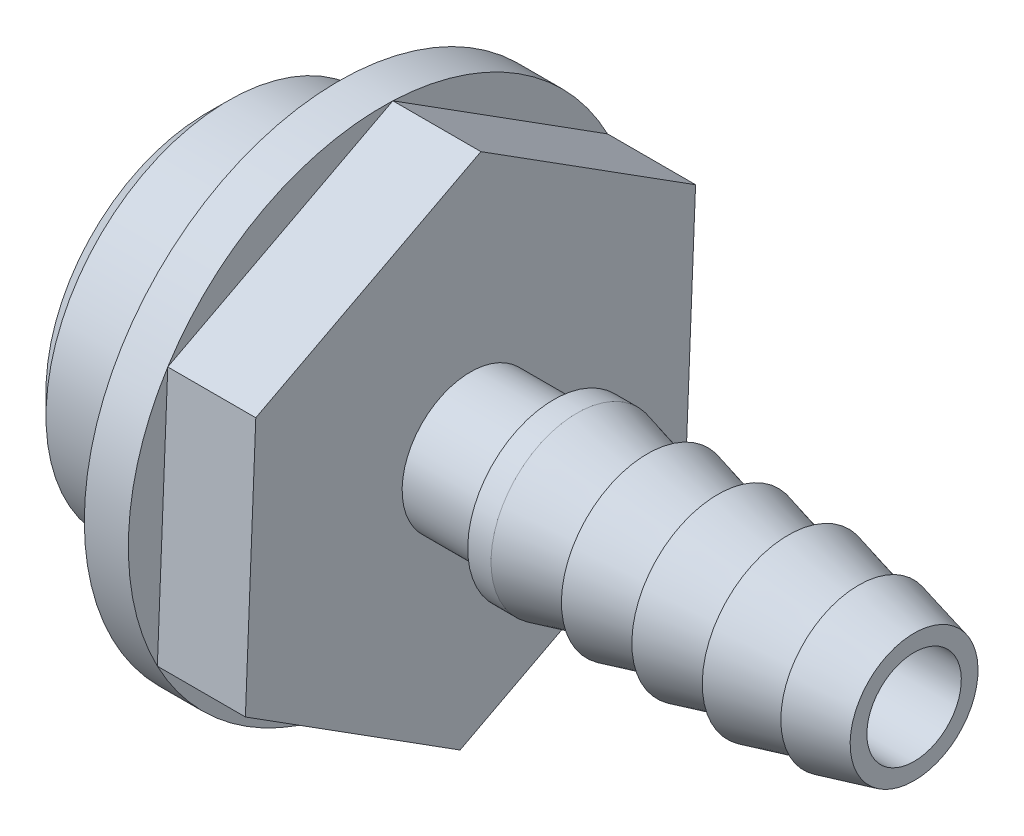
SolidWorks part; units mm, degrees
ref_plane "Plan de face" through (0, 0, 0) normal (0, 0, 1) x (1, 0, 0)
ref_plane "Plan de dessus" through (0, 0, 0) normal (0, 1, 0) x (1, 0, 0)
ref_plane "Plan de droite" through (0, 0, 0) normal (1, 0, 0) x (0, 0, -1)
ref_plane "Plan1"
sketch "Esquisse1" plane through (0, 0, 0) normal (0, 0, 1) x (1, 0, 0)
  line L0 (0, 1.703) -> (16, 1.703)
  line L1 (16, 1.703) -> (16, 3.1)
  line L2 (16, 3.1) -> (14, 3.1)
  line L3 (14, 3.1) -> (14, 2.465)
  line L4 (14, 2.465) -> (11.46, 3.1)
  line L5 (11.46, 3.1) -> (11.46, 2.465)
  line L6 (11.46, 2.465) -> (8.92, 3.1)
  line L7 (8.92, 3.1) -> (8.92, 2.465)
  line L8 (8.92, 2.465) -> (6.38, 3.1)
  line L9 (6.38, 3.1) -> (6.38, 2.465)
  line L10 (6.38, 2.465) -> (3.84, 3.1)
  line L11 (3.84, 3.1) -> (3, 3.1)
  line L12 (3, 3.1) -> (3, 2.465)
  line L13 (3, 2.465) -> (0, 2.465)
  line L14 (0, 2.465) -> (0, 1.703)
  line L15 (0, 0) -> (142.9139, 0) construction
  dimension "D2" = 16
  dimension "D3" = 2
  dimension "D4" = 2.54
  dimension "D5" = 2.54
  dimension "D6" = 2.54
  dimension "D7" = 2.54
  dimension "D8" = 165.964
  dimension "D9" = 16
  dimension "D10" = 16
  dimension "D11" = 3
  dimension "D12" = 0.762
  dimension "D13" = 0.635
  dimension "D14" = 1.397
  dimension "D15" = 3.1
revolve "Revolution1" add sketch "Esquisse1" angle 360 about L15
chamfer "Chamfer1" distance 0.7938 distance2 3.175 1 edges at (16, -3.1, 0) first distance on face at (16, -3.1, 0)
ref_plane "Plan2"
sketch "Esquisse2" plane through (0, 0, 0) normal (-1, 0, 0) x (0, 0, 1)
  line L0 (0.3759, -9.1577) -> (-7.7429, -4.9044)
  line L1 (-7.7429, -4.9044) -> (-8.1188, 4.2533)
  line L2 (-8.1188, 4.2533) -> (-0.3759, 9.1577)
  line L3 (-0.3759, 9.1577) -> (7.7429, 4.9044)
  line L4 (7.7429, 4.9044) -> (8.1188, -4.2533)
  line L5 (8.1188, -4.2533) -> (0.3759, -9.1577)
  dimension "D1" = 15.875
extrude "Extrusion1" add sketch "Esquisse2" along normal blind 3.175
sketch "Esquisse3" plane through (-3.175, 0, 0) normal (-1, 0, 0) x (0, 0, 1)
  circle A0 centre (0, 0) radius 9.1654
extrude "Extrusion2" add sketch "Esquisse3" along normal blind 1.5875
sketch "Esquisse4" plane through (-4.7625, 0, 0) normal (-1, 0, 0) x (0, 0, 1)
  circle A0 centre (0, 0) radius 6.5786
  dimension "D1" = 13.1572
extrude "Thread1" add sketch "Esquisse4" along normal blind 4.7625
cosmetic thread "Représentation de filetage1" parameters "D2"=0
chamfer "Chamfer2" distance 0.7938 distance2 0.7938 1 edges at (-9.525, 0, 6.5786)
sketch "Sketch1" plane through (0, 0, 0) normal (0, 1, 0) x (1, 0, 0)
  line L0 (0, -1.703) -> (-2, -1.703)
  line L1 (0, -1.703) -> (0, 1.703) construction
  line L2 (-2, -1.703) -> (-2, -5)
  line L3 (-2, -5) -> (-9.525, -5)
  line L4 (-9.525, 5.7849) -> (-9.525, -5.7849) construction
  line L5 (-9.525, -5) -> (-9.525, 0)
  line L6 (-9.525, 0) -> (0, 0)
  line L7 (0, 0) -> (0, -1.703)
  line L8 (0, -0.3759) -> (0, -8.1188) construction
  dimension "D1" = 5
  dimension "D2" = 2
revolve "Cut-Revolve1" cut sketch "Sketch1" angle 360 about L6
chamfer "Chamfer4" distance 1 angle 45 1 edges at (-2, 0, 1.703)
